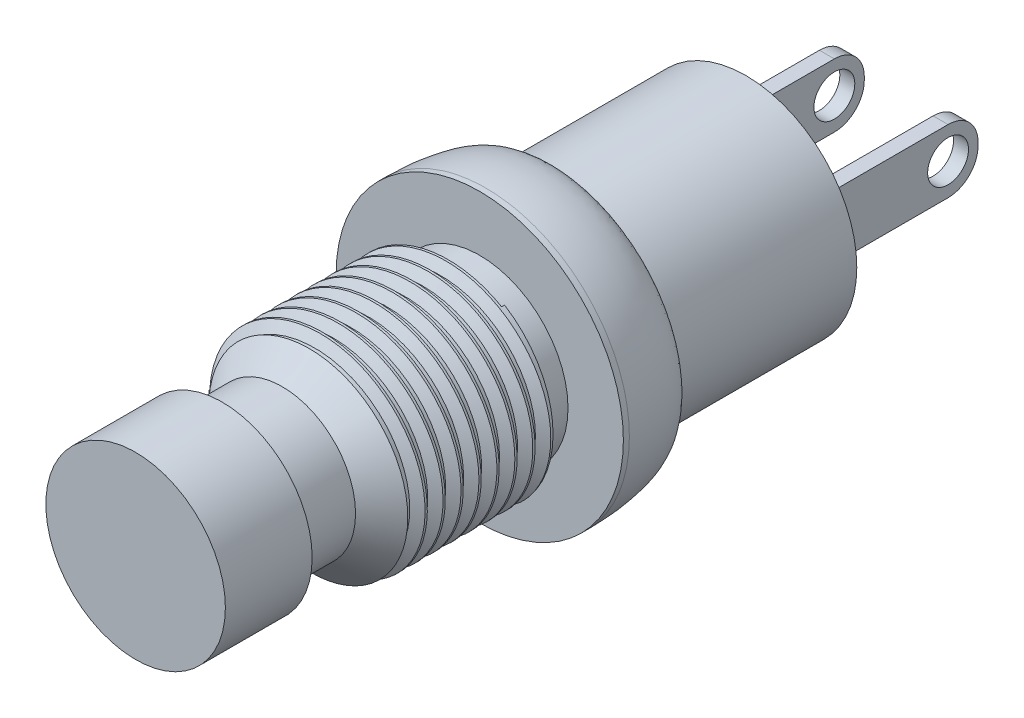
SolidWorks part; units mm, degrees
ref_plane "Front Plane" through (0, 0, 0) normal (0, 0, 1) x (1, 0, 0)
ref_plane "Top Plane" through (0, 0, 0) normal (0, 1, 0) x (1, 0, 0)
ref_plane "Right Plane" through (0, 0, 0) normal (1, 0, 0) x (0, 0, -1)
sketch "Sketch1" plane through (0, 0, 0) normal (0, 0, 1) x (1, 0, 0)
  circle A0 centre (0, 0) radius 3.7
  dimension "D1" = 7.4
extrude "Boss-Extrude1" add sketch "Sketch1" along normal blind 6.5
sketch "Sketch2" plane through (0, 0, 6.5) normal (0, 0, 1) x (1, 0, 0)
  circle A0 centre (0, 0) radius 4.8
  dimension "D1" = 9.6
extrude "Boss-Extrude2" add sketch "Sketch2" along normal blind 2.4
fillet "Fillet1" radius 0.5 1 edges at (4.8, 0, 6.5) second distance 2.2 first distance on face at (3.7, 0, 6.5)
sketch "Sketch3" plane through (0, 0, 8.9) normal (0, 0, 1) x (1, 0, 0)
  circle A0 centre (0, 0) radius 3.45
  dimension "D1" = 6.9
extrude "Boss-Extrude3" add sketch "Sketch3" along normal blind 6.6
chamfer "Chamfer1" distance 1 angle 45 1 edges at (3.45, 0, 15.5)
sketch "Sketch9" plane through (0, 0, 15.5) normal (0, 0, 1) x (1, 0, 0)
  circle A0 centre (0, 0) radius 2.45
  dimension "D1" = 4.9
extrude "Boss-Extrude4" add sketch "Sketch9" along normal blind 2
thread "Thread1" pitch 0.6 method cut profile "Thread Profile1" start angle 2, offset 0.5, length 5, pitch 0.6, diameter 6.9
ref_plane "Plane1" through (-3.4479, 0.1204, 15) normal (-0.0349, -0.9994, 0) x (-0.9994, 0.0349, 0)
sketch "Thread Profile1" plane through (-3.4479, 0.1204, 15) normal (-0.0349, -0.9994, 0) x (-0.9994, 0.0349, 0)
  line L0 (0, 0) -> (0, 0.6) construction
  line L11 (0, 0) -> (0, 0.525)
  line L12 (0, 0.525) -> (-0.3248, 0.3375)
  line L13 (-0.3248, 0.3375) -> (-0.3248, 0.1875)
  line L15 (-0.3248, 0.1875) -> (0, 0)
  line L17 (-0.3248, 0.2625) -> (0, 0.2625) construction
  point P2 (0, 0)
  dimension "Pitch" = 0.6
  dimension "Profile_Angle" = 60
  dimension "Profile_Land" = 0.15
  dimension "Profile_Height" = 0.3248
sketch "Sketch10" plane through (0, 0, 8.9) normal (0, 0, 1) x (1, 0, 0)
  circle A0 centre (0, 0) radius 2.95
  circle A1 centre (0, 0) radius 3.45
  dimension "D1" = 5.9
extrude "Cut-Extrude1" cut sketch "Sketch10" along normal blind 1
sketch "Sketch11" plane through (0, 0, 17.5) normal (0, 0, 1) x (1, 0, 0)
  circle A0 centre (0, 0) radius 3
extrude "Boss-Extrude5" add sketch "Sketch11" along normal blind 2.9
sketch "Sketch12" plane through (0, 0, 0) normal (0, 0, -1) x (-1, 0, 0)
  line L0 (0, 1.06) -> (0, -1.06) construction
  line L1 (-2.15, 1.06) -> (2.15, 1.06) construction
  line L2 (-2.15, 1.06) -> (-2.15, -1.06) construction
  line L3 (-2.15, -1.06) -> (2.15, -1.06) construction
  line L4 (2.15, 1.06) -> (2.15, -1.06) construction
  line L5 (-2.15, 1.06) -> (2.15, -1.06) construction
  line L6 (-2.15, -1.06) -> (2.15, 1.06) construction
  line L7 (2.15, -1.06) -> (1.65, -1.06)
  line L8 (-2.15, 1.06) -> (-1.65, 1.06)
  line L9 (-2.15, 1.06) -> (-2.15, -1.06)
  line L10 (-2.15, -1.06) -> (-1.65, -1.06)
  line L11 (-1.65, 1.06) -> (-1.65, -1.06)
  line L12 (2.15, 1.06) -> (2.15, -1.06)
  line L13 (2.15, 1.06) -> (1.65, 1.06)
  line L14 (1.65, 1.06) -> (1.65, -1.06)
  point P0 (0, 0)
  dimension "D1" = 4.3
  dimension "D2" = 2.12
  dimension "D3" = 0.5
extrude "Boss-Extrude6" add sketch "Sketch12" along normal blind 5.6
fillet "Fillet2" radius 1 4 edges at (-1.9, -1.06, -5.6) (-1.9, 1.06, -5.6) (1.9, -1.06, -5.6) (1.9, 1.06, -5.6)
sketch "Sketch13" plane through (2.15, 0, 0) normal (1, 0, 0) x (0, 0, -1)
  line L0 (4.6, 1.06) -> (4.6, -1.06) construction
  circle A0 centre (4.6, 0) radius 0.6828
extrude "Cut-Extrude2" cut sketch "Sketch13" against normal blind 5.6
